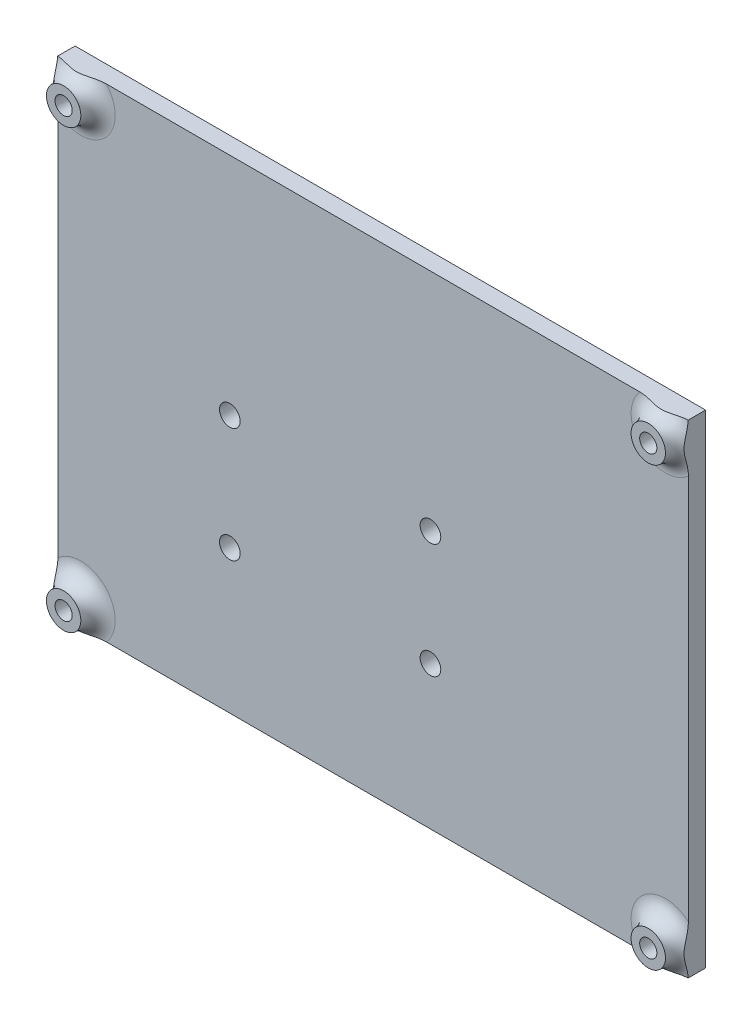
SolidWorks part; units mm, degrees
ref_plane "Front Plane" through (0, 0, 0) normal (0, 0, 1) x (1, 0, 0)
ref_plane "Top Plane" through (0, 0, 0) normal (0, 1, 0) x (1, 0, 0)
ref_plane "Right Plane" through (0, 0, 0) normal (1, 0, 0) x (0, 0, -1)
sketch "Sketch1" plane through (0, 0, 0) normal (0, 0, 1) x (1, 0, 0)
  line L0 (55, 42.15) -> (51, 42.15) construction
  line L1 (-55, -42.15) -> (55, -42.15)
  line L2 (-55, -42.15) -> (-55, 42.15)
  line L3 (-55, 42.15) -> (55, 42.15)
  line L4 (55, -42.15) -> (55, 42.15)
  line L5 (-55, -42.15) -> (55, 42.15) construction
  line L6 (-55, 42.15) -> (55, -42.15) construction
  line L7 (51, 42.15) -> (51, 38.15) construction
  line L8 (0, 0) -> (14.3892, 0) construction
  line L9 (0, 0) -> (0, 17.3682) construction
  line L10 (-51, 38.15) -> (-55, 38.15) construction
  line L11 (-51, 38.15) -> (-51, 42.15) construction
  line L12 (-55, -42.15) -> (-55, -17.15) construction
  line L13 (-55, -17.15) -> (-25, -17.15) construction
  line L14 (-25, -17.15) -> (10, -17.15) construction
  line L15 (-25, -17.15) -> (-25, 2.85) construction
  line L16 (10, -17.15) -> (10, 2.85) construction
  circle A0 centre (51, 38.15) radius 1.5
  circle A1 centre (-51, 38.15) radius 1.5
  circle A2 centre (51, -38.15) radius 1.5
  circle A3 centre (-51, -38.15) radius 1.5
  circle A4 centre (-25, -17.15) radius 1.8
  circle A5 centre (-25, 2.85) radius 1.8
  circle A6 centre (10, 2.85) radius 1.8
  circle A7 centre (10, -17.15) radius 1.8
  point P0 (0, 0)
extrude "Boss-Extrude1" add sketch "Sketch1" along normal blind 3
sketch "Sketch2" plane through (0, 0, 0) normal (0, 0, 1) x (1, 0, 0)
  line L0 (0, 0) -> (0, 8.6543) construction
  line L1 (0, 0) -> (12.5985, 0) construction
  circle A0 centre (-51, 38.15) radius 1.5
  circle A1 centre (-51, 38.15) radius 3
  circle A2 centre (51, 38.15) radius 3
  circle A3 centre (51, 38.15) radius 1.5
  circle A4 centre (51, -38.15) radius 1.5
  circle A5 centre (51, -38.15) radius 3
  circle A6 centre (-51, -38.15) radius 3
  circle A7 centre (-51, -38.15) radius 1.5
extrude "Boss-Extrude2" add sketch "Sketch2" along normal blind 3 from surface starting at face at (0, 0, 3)
fillet "Fillet1" radius 3 4 edges at (48, -38.15, 3) (48, 38.15, 3) (-54, 38.15, 3) (-54, -38.15, 3)
